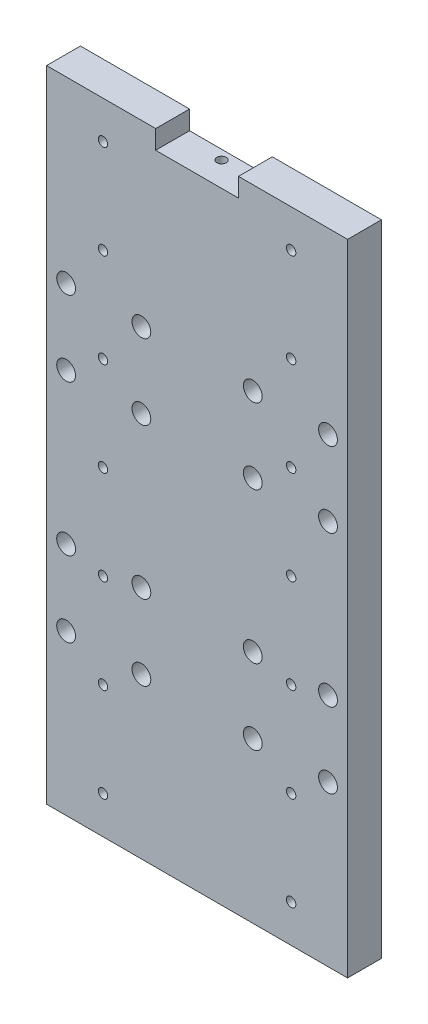
SolidWorks part; units mm, degrees
ref_plane "Front" through (0, 0, 0) normal (0, 0, 1) x (1, 0, 0)
ref_plane "Top" through (0, 0, 0) normal (0, 1, 0) x (1, 0, 0)
ref_plane "Right" through (0, 0, 0) normal (1, 0, 0) x (0, 0, -1)
sketch "Esquisse1" plane through (0, 0, 0) normal (0, 0, 1) x (1, 0, 0)
  line L1 (0, 0) -> (80, 0)
  line L2 (0, 0) -> (0, 170)
  line L3 (0, 170) -> (80, 170)
  line L4 (80, 0) -> (80, 170)
  dimension "D1" = 80
  dimension "D2" = 170
extrude "Boss.-Extru.1" add sketch "Esquisse1" along normal blind 9
sketch "Esquisse2" plane through (0, 0, 9) normal (0, 0, 1) x (1, 0, 0)
  line L0 (40, 0) -> (40, 170) construction
  line L1 (0, 0) -> (80, 0) construction
  line L2 (80, 170) -> (0, 170) construction
  line L3 (15, 10) -> (15, 35) construction
  circle A0 centre (15, 10) radius 1.25
  circle A1 centre (65, 10) radius 1.25
  circle A2 centre (15, 35) radius 1.25
  circle A3 centre (65, 35) radius 1.25
  circle A4 centre (15, 60) radius 1.25
  circle A5 centre (65, 60) radius 1.25
  circle A6 centre (15, 85) radius 1.25
  circle A7 centre (65, 85) radius 1.25
  circle A8 centre (15, 110) radius 1.25
  circle A9 centre (65, 110) radius 1.25
  circle A10 centre (15, 135) radius 1.25
  circle A11 centre (65, 135) radius 1.25
  circle A12 centre (15, 160) radius 1.25
  circle A13 centre (65, 160) radius 1.25
  circle A14 centre (15, 185) radius 1.25
  circle A15 centre (65, 185) radius 1.25
  dimension "D2" = 2.5
  dimension "D1" = 50
  dimension "D3" = 10
  dimension "D5" = 25
  dimension "D4" = 8
extrude "Enlèv. mat.-Extru.1" cut sketch "Esquisse2" against normal through all
sketch "Esquisse4" plane through (0, 0, 9) normal (0, 0, 1) x (1, 0, 0)
  line L0 (40, 170) -> (40, 165) construction
  line L1 (80, 170) -> (0, 170) construction
  line L2 (51, 165) -> (29, 165)
  line L3 (29, 165) -> (29, 170)
  line L4 (29, 170) -> (51, 170)
  line L5 (51, 165) -> (51, 170)
  dimension "D1" = 22
  dimension "D2" = 5
extrude "Enlèv. mat.-Extru.3" cut sketch "Esquisse4" against normal through all
sketch "Esquisse5" plane through (0, 165, 0) normal (0, 1, 0) x (1, 0, 0)
  line L0 (40, 0) -> (40, -2.5) construction
  line L3 (29, 0) -> (51, 0) construction
  circle A0 centre (40, -2.5) radius 1.25
  dimension "D1" = 2.5
  dimension "D2" = 2.5
extrude "Enlèv. mat.-Extru.4" cut sketch "Esquisse5" against normal blind 10
sketch "Esquisse6" plane through (0, 0, 9) normal (0, 0, 1) x (1, 0, 0)
  line L0 (74.8, 122.5) -> (74.8, 82.5) construction
  line L1 (40, 165) -> (40, 0) construction
  line L2 (29, 165) -> (51, 165) construction
  line L3 (0, 0) -> (80, 0) construction
  line L5 (74.8, 82.5) -> (40, 82.5) construction
  line L6 (5.2, 122.5) -> (5.2, 82.5) construction
  line L7 (74.8, 122.5) -> (64.8, 122.5) construction
  line L8 (64.8, 122.5) -> (64.8, 124.5729) construction
  circle A0 centre (74.8, 122.5) radius 2.5
  circle A1 centre (74.8, 62.5) radius 2.5
  circle A2 centre (74.8, 102.5) radius 2.5
  circle A3 centre (74.8, 42.5) radius 2.5
  circle A4 centre (5.2, 42.5) radius 2.5
  circle A5 centre (5.2, 102.5) radius 2.5
  circle A6 centre (5.2, 62.5) radius 2.5
  circle A7 centre (5.2, 122.5) radius 2.5
  circle A8 centre (54.8, 102.5) radius 2.5
  circle A9 centre (54.8, 122.5) radius 2.5
  circle A10 centre (54.8, 42.5) radius 2.5
  circle A11 centre (54.8, 62.5) radius 2.5
  circle A12 centre (25.2, 62.5) radius 2.5
  circle A13 centre (25.2, 42.5) radius 2.5
  circle A14 centre (25.2, 122.5) radius 2.5
  circle A15 centre (25.2, 102.5) radius 2.5
  dimension "D3" = 5
  dimension "D5" = 20
  dimension "D1" = 34.8
  dimension "D2" = 20
  dimension "D4" = 20
extrude "Enlèv. mat.-Extru.5" cut sketch "Esquisse6" against normal through all
